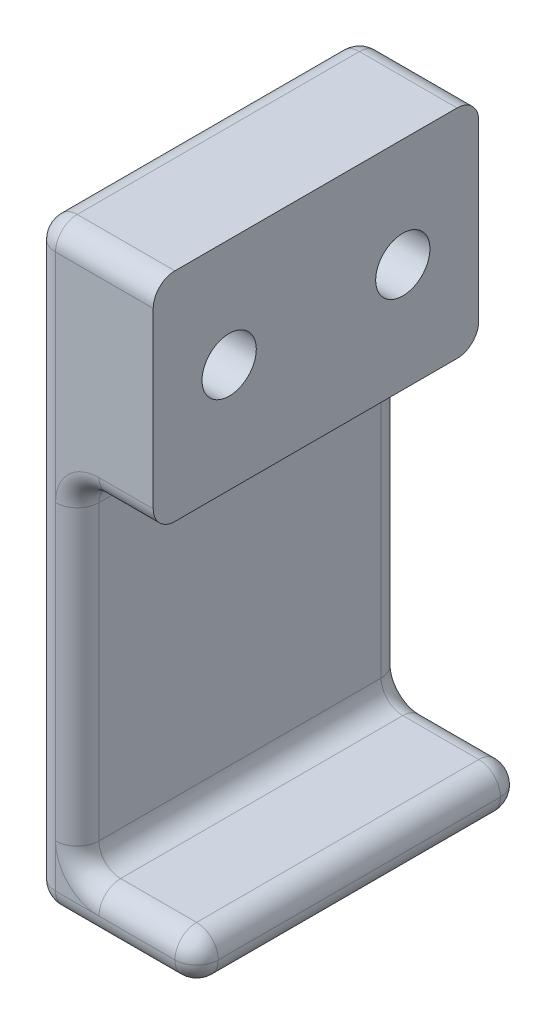
SolidWorks part; units mm, degrees
ref_plane "정면" through (0, 0, 0) normal (0, 0, 1) x (1, 0, 0)
ref_plane "윗면" through (0, 0, 0) normal (0, 1, 0) x (1, 0, 0)
ref_plane "우측면" through (0, 0, 0) normal (1, 0, 0) x (0, 0, -1)
sketch "스케치1" plane through (0, 0, 0) normal (0, 0, 1) x (1, 0, 0)
  line L1 (-41.8182, 31.1364) -> (-37.8182, 31.1364)
  line L2 (-41.8182, 31.1364) -> (-41.8182, -23.8636)
  line L3 (-41.8182, -23.8636) -> (-32.7273, -23.8636)
  line L4 (-37.8182, 31.1364) -> (-37.8182, -19.8636)
  line L5 (-32.7273, -23.8636) -> (-26.8182, -23.8636)
  line L7 (-37.8182, -19.8636) -> (-26.8182, -19.8636)
  line L8 (-26.8182, -23.8636) -> (-26.8182, -19.8636)
  dimension "D1" = 55
  dimension "D2" = 15
  dimension "D3" = 4
  dimension "D4" = 4
extrude "보스-돌출1" add sketch "스케치1" along normal blind 30
sketch "스케치3" plane through (0, 0, 30) normal (0, 0, 1) x (1, 0, 0)
  line L0 (-30.8182, 10.8364) -> (-30.8182, 4.0864) construction
  line L1 (-37.8182, 31.1364) -> (-30.8182, 31.1364)
  line L2 (-37.8182, 31.1364) -> (-37.8182, 11.1364)
  line L3 (-37.8182, 11.1364) -> (-30.8182, 11.1364)
  line L4 (-30.8182, 31.1364) -> (-30.8182, 11.1364)
  dimension "D1" = 20
extrude "보스-돌출2" add sketch "스케치3" against normal up to surface (30 mm away) up to face at (-35.4848, -4.197, 0)
sketch "스케치2" plane through (-41.8182, 0, 0) normal (-1, 0, 0) x (0, 0, 1)
  line L0 (30, 31.1364) -> (0, 31.1364) construction
  line L1 (0, 31.1364) -> (0, -23.8636) construction
  line L2 (30, 31.1364) -> (30, -23.8636) construction
  circle A0 centre (7, 21.1364) radius 2.5
  circle A1 centre (23, 21.1364) radius 2.5
  dimension "D1" = 5
  dimension "D4" = 7
  dimension "D2" = 10
  dimension "D3" = 7
extrude "컷-돌출1" cut sketch "스케치2" against normal blind 30
fillet "필렛1" radius 2 2 edges at (-37.8182, 11.1364, 15) (-37.8182, -19.8636, 15)
fillet "필렛2" radius 2 1 edges at (-41.8182, -23.8636, 15)
fillet "필렛3" radius 2 3 edges at (-26.8182, -23.8636, 15) (-26.8182, -19.8636, 15) (-41.8182, 31.1364, 15)
fillet "필렛5" radius 2 24 edges at (-35.3182, 31.1364, 0) (-41.2324, 30.5506, 0) (-33.3182, 11.1364, 0) (-37.2324, 10.5506, 0) (-37.8182, -4.3636, 0) (-37.2324, -19.2778, 0) (-32.3182, -19.8636, 0) (-27.404, -20.4494, 0) (-27.404, -23.2778, 0) (-34.3182, -23.8636, 0) (-41.2324, -23.2778, 0) (-35.3182, 31.1364, 30) (-41.2324, 30.5506, 30) (-33.3182, 11.1364, 30) (-37.2324, 10.5506, 30) (-37.8182, -4.3636, 30) (-37.2324, -19.2778, 30) (-32.3182, -19.8636, 30) (-27.404, -20.4494, 30) (-27.404, -23.2778, 30) (-34.3182, -23.8636, 30) (-41.2324, -23.2778, 30) (-41.8182, 3.6364, 0) (-41.8182, 3.6364, 30)
sketch "스케치4" plane through (-41.8182, 0, 0) normal (-1, 0, 0) x (0, 0, 1)
  circle A0 centre (7, 21.1364) radius 5
  circle A1 centre (23, 21.1364) radius 5
  dimension "D1" = 10
extrude "컷-돌출2" cut sketch "스케치4" against normal blind 5
